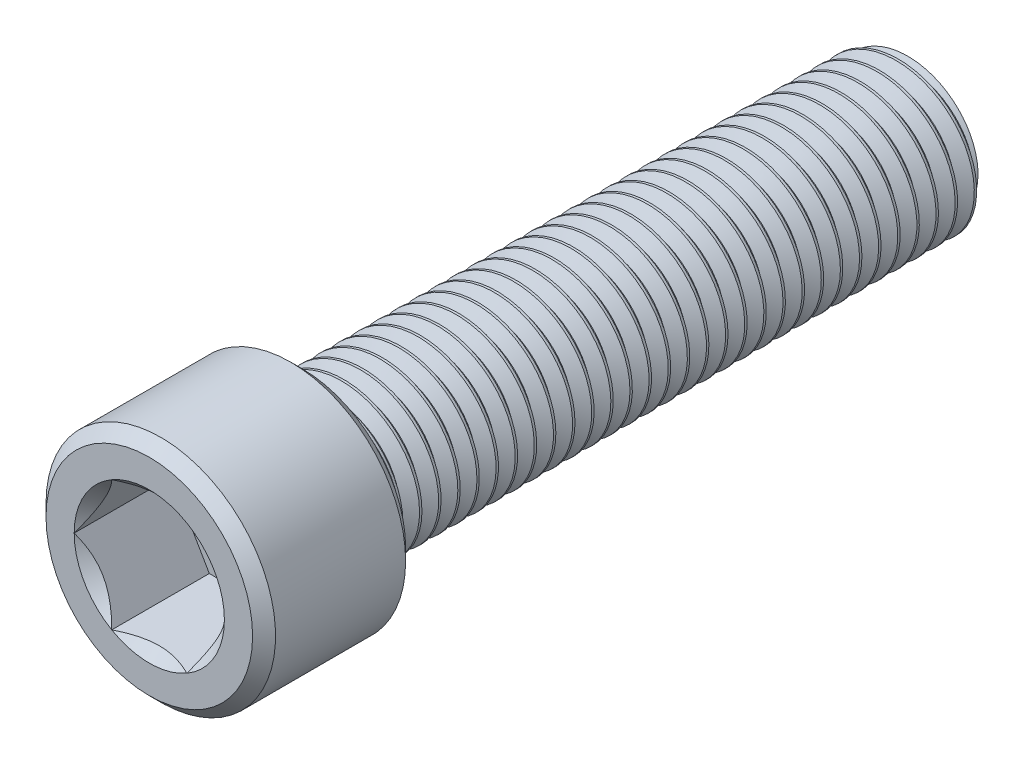
SolidWorks part; units mm, degrees
ref_plane "Front Plane" through (0, 0, 0) normal (0, 0, 1) x (1, 0, 0)
ref_plane "Top Plane" through (0, 0, 0) normal (0, 1, 0) x (1, 0, 0)
ref_plane "Right Plane" through (0, 0, 0) normal (1, 0, 0) x (0, 0, -1)
sketch "Sketch1" plane through (0, 0, 0) normal (0, 0, 1) x (1, 0, 0)
  circle A0 centre (0, 0) radius 10
  dimension "BODY DIAMETER" = 20
extrude "Boss-Extrude1" add sketch "Sketch1" along normal blind 80
sketch "Sketch2" plane through (0, 0, 0) normal (0, 0, -1) x (-1, 0, 0)
  circle A1 centre (0, 0) radius 10
  circle A2 centre (0, 0) radius 10
  dimension "D1" = 0
curve "Helix/Spiral1" pitch 2.5 height 105 turns 42 parameters "PITCH"=2.5
ref_plane "Plane1" through (0, 10, 0) normal (-0.9992, 0, 0.0398) x (0.0398, 0, 0.9992)
sketch "Sketch3" plane through (0, 10, 0) normal (-0.9992, 0, 0.0398) x (0.0398, 0, 0.9992)
  line L0 (0, 0) -> (-2.187, 0)
  line L1 (-2.187, 0) -> (-1.25, -1.6229)
  line L2 (-1.25, -1.6229) -> (-0.937, -1.6229)
  line L3 (-0.937, -1.6229) -> (0, 0)
  line L4 (-1.0935, -1.6229) -> (-1.0935, 0) construction
  line L5 (-1.7185, -0.8115) -> (-0.4685, -0.8115) construction
  dimension "D1" = 60
  dimension "THREAD DIM1" = 0.313
  dimension "THREAD DIM 2" = 1.25
sweep "Cut-Sweep1" cut profiles "Sketch3" path "Helix/Spiral1"
sketch "Sketch4" plane through (0, 0, 0) normal (1, 0, 0) x (0, 0, -1)
  line L0 (0, 11) -> (-2.0144, 11)
  line L1 (-2.0144, 11) -> (0, 8.1231)
  line L2 (0, 8.1231) -> (0, 11)
  line L3 (0, 10) -> (2.1853, 10) construction
  line L4 (0, 0) -> (1.7976, 0) construction
  dimension "D1" = 55
  dimension "D2" = 1
  dimension "D3" = 0.254
revolve "Cut-Revolve1" cut sketch "Sketch4" angle 360 about L4
sketch "Sketch5" plane through (0, 0, 80) normal (0, 0, 1) x (1, 0, 0)
  circle A0 centre (0, 0) radius 15
  dimension "HEAD DIAMETER" = 30
extrude "Boss-Extrude2" add sketch "Sketch5" along normal blind 20
sketch "Sketch6" plane through (0, 0, 100) normal (0, 0, 1) x (1, 0, 0)
  line L1 (4.9075, 8.5) -> (-4.9075, 8.5)
  line L2 (-4.9075, 8.5) -> (-9.815, 0)
  line L3 (-9.815, 0) -> (-4.9075, -8.5)
  line L4 (-4.9075, -8.5) -> (4.9075, -8.5)
  line L5 (4.9075, -8.5) -> (9.815, 0)
  line L6 (9.815, 0) -> (4.9075, 8.5)
  circle A0 centre (0, 0) radius 8.5 construction
  dimension "HEX SOCKET SIZE" = 17
extrude "Cut-Extrude1" cut sketch "Sketch6" against normal blind 12.75
sketch "Sketch7" plane through (0, 0, 100) normal (0, 0, 1) x (1, 0, 0)
  circle A0 centre (0, 0) radius 9.815
extrude "Cut-Extrude2" cut sketch "Sketch7" against normal through all draft 45
chamfer "Chamfer1" distance 1.5 angle 45 2 edges at (15, 0, 80) (15, 0, 100)
